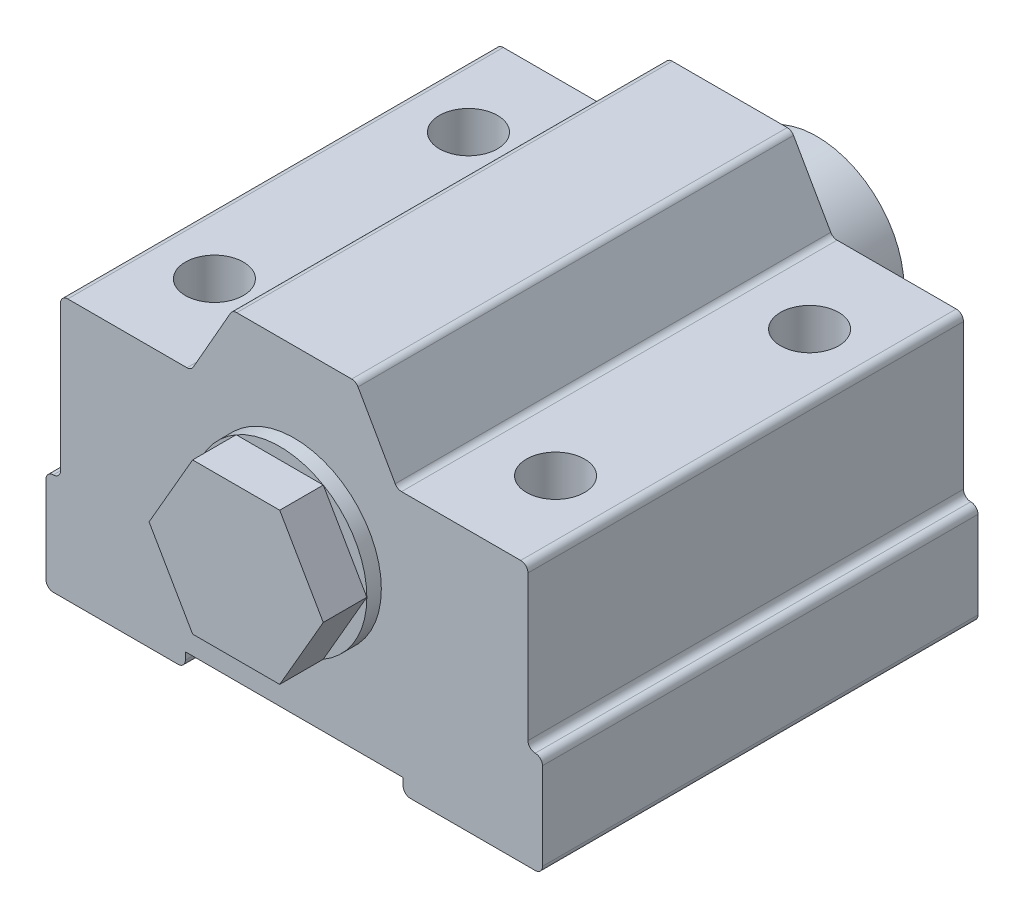
SolidWorks part; units mm, degrees
ref_plane "前视基准面" through (0, 0, 0) normal (0, 0, 1) x (1, 0, 0)
ref_plane "上视基准面" through (0, 0, 0) normal (0, 1, 0) x (1, 0, 0)
ref_plane "右视基准面" through (0, 0, 0) normal (1, 0, 0) x (0, 0, -1)
other "Configuration Table"
sketch "草图2" plane through (0, 0, 0) normal (0, 0, 1) x (1, 0, 0)
  line L0 (-17.1, 0) -> (17.1, 0)
  line L1 (-17.1, 0) -> (-17.1, 18)
  line L2 (-17.1, 18) -> (-7.1, 18)
  line L3 (-7.1, 18) -> (-4.25, 23)
  line L4 (-4.25, 23) -> (4.25, 23)
  line L5 (4.25, 23) -> (7.1, 18)
  line L6 (7.1, 18) -> (17.1, 18)
  line L7 (17.1, 18) -> (17.1, 0)
  circle A2 centre (0, 11.5) radius 6
  point P2 (0, 0)
  point P3 (0, 23)
  dimension "D3" = 12
  dimension "D1" = 34.2
  dimension "D2" = 18
  dimension "8.5" = 8.5
  dimension "D4" = 10
  dimension "D5" = 23
  dimension "10" = 11.5
extrude "凸台-拉伸1" add sketch "草图2" along normal blind 30 contours L7 L6 L5 L4 L3 L2 L1 L0 A2 | A2 region at (-16.6879, 9, 0) region at (0, 11.5, 0)
extrude "凸台-拉伸2" add sketch "草图2<3>" against normal blind 6 contours A2 region at (0, 11.5, 0)
sketch "草图2<3>" plane through (0, 0, 0) normal (0, 0, 1) x (1, 0, 0) same geometry as "草图2"
extrude "凸台-拉伸3" add sketch "草图2<4>" along normal blind 1 from surface contours A2 starting at face at (0, 14.75, 30)
sketch "草图2<4>" plane through (0, 0, 0) normal (0, 0, 1) x (1, 0, 0) same geometry as "草图2"
sketch "草图4" plane through (0, 0, 0) normal (0, -1, 0) x (1, 0, 0)
  line L0 (-11.75, 6.25) -> (11.75, 6.25) construction
  circle A0 centre (11.75, 23.75) radius 2
  circle A1 centre (11.75, 6.25) radius 2
  circle A2 centre (-11.75, 23.75) radius 2
  circle A3 centre (-11.75, 6.25) radius 2
  point P8 (0, 6.25)
  dimension "D1" = 4
  dimension "D2" = 17.5
  dimension "D3" = 23.5
  dimension "D4" = 6.25
extrude "切除-拉伸1" cut sketch "草图4" against normal up to next
sketch "草图5" plane through (0, 0, 30) normal (0, 0, 1) x (1, 0, 0)
  line L0 (16.1, 18) -> (16.1, 7)
  line L1 (16.1, 7) -> (17.1, 7)
  line L2 (-16.1, 18) -> (-16.1, 7)
  line L3 (-16.1, 7) -> (-17.1, 7)
  line L4 (-7.5, 1) -> (7.5, 1)
  line L5 (-7.5, 1) -> (-7.5, 0)
  line L6 (-17.1, 0) -> (17.1, 0) construction
  line L7 (7.5, 1) -> (7.5, 0)
  line L8 (17.1, 0) -> (17.1, 18)
  line L9 (17.1, 18) -> (7.1, 18)
  line L10 (7.1, 18) -> (4.25, 23)
  line L11 (4.25, 23) -> (-4.25, 23)
  line L12 (-4.25, 23) -> (-7.1, 18)
  line L13 (-7.1, 18) -> (-17.1, 18)
  line L14 (-17.1, 18) -> (-17.1, 0)
  line L15 (-17.1, 0) -> (17.1, 0)
  line L16 (17.1, 7) -> (17.1, 18)
  line L17 (17.1, 18) -> (16.1, 18)
  line L21 (-16.1, 18) -> (-17.1, 18)
  line L22 (-17.1, 18) -> (-17.1, 7)
  line L24 (-7.5, 0) -> (7.5, 0)
  point P24 (0, 1)
  dimension "D2" = 11
  dimension "D3" = 1
  dimension "D4" = 1
  dimension "D5" = 15
  dimension "D1" = 0
extrude "切除-拉伸2" cut sketch "草图5" against normal up to next
fillet "圆角1" radius 0.5 14 edges at (17.1, 0, 15) (7.5, 0, 15) (-7.5, 0, 15) (-17.1, 0, 15) (-17.1, 7, 15) (-16.1, 7, 15) (-16.1, 18, 15) (17.1, 7, 15) (16.1, 7, 15) (16.1, 18, 15) (-7.1, 18, 15) (7.1, 18, 15) (-4.25, 23, 15) (4.25, 23, 15)
sketch "草图6" plane through (0, 0, 31) normal (0, 0, 1) x (1, 0, 0)
  line L0 (-3, 16.6962) -> (3, 16.6962)
  line L1 (3, 16.6962) -> (6, 11.5)
  line L2 (6, 11.5) -> (3, 6.3038)
  line L3 (3, 6.3038) -> (-3, 6.3038)
  line L4 (-3, 6.3038) -> (-6, 11.5)
  line L5 (-6, 11.5) -> (-3, 16.6962)
  circle A0 centre (0, 11.5) radius 6 construction
  circle A1 centre (0, 11.5) radius 6 construction
  circle A2 centre (0, 11.5) radius 6 construction
  point P2 (2.6473, 16.0428)
  point P5 (0, 11.5)
  point P7 (0, 16.6962)
  point P8 (3, 16.6962)
  point P19 (0, 11.5)
  dimension "D1" = 6
extrude "凸台-拉伸4" add sketch "草图6" along normal blind 3
